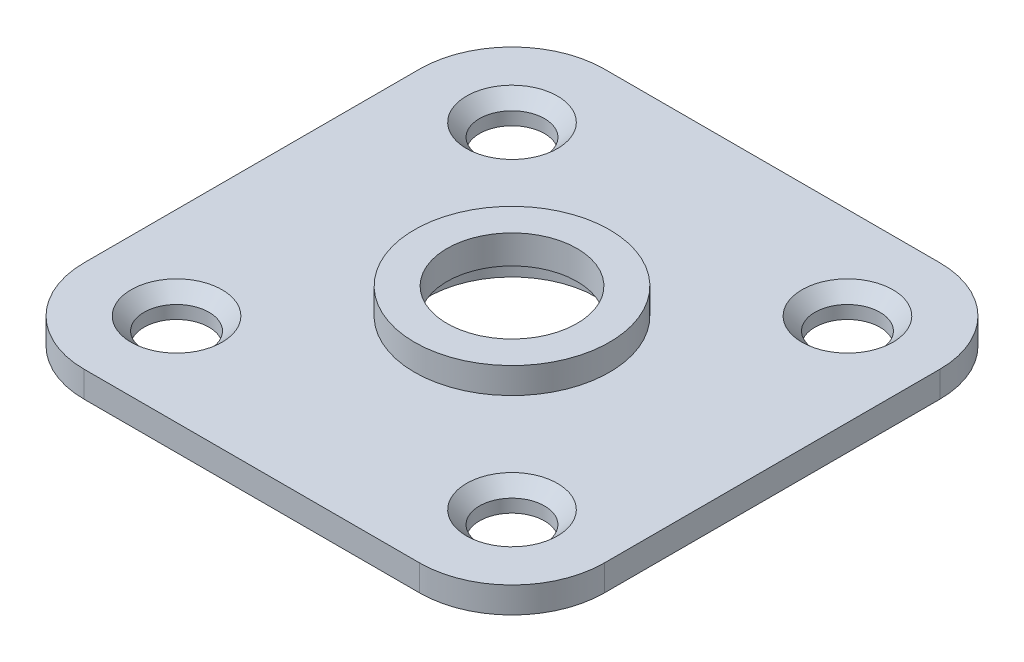
SolidWorks part; units mm, degrees
ref_plane "Front Plane" through (0, 0, 0) normal (0, 0, 1) x (1, 0, 0)
ref_plane "Top Plane" through (0, 0, 0) normal (0, 1, 0) x (1, 0, 0)
ref_plane "Right Plane" through (0, 0, 0) normal (1, 0, 0) x (0, 0, -1)
sketch "Sketch2" plane through (0, 0, 0) normal (0, 1, 0) x (1, 0, 0)
  line L1 (-25.4, 25.4) -> (25.4, 25.4)
  line L2 (-25.4, 25.4) -> (-25.4, -25.4)
  line L3 (-25.4, -25.4) -> (25.4, -25.4)
  line L4 (25.4, 25.4) -> (25.4, -25.4)
  line L5 (-25.4, 25.4) -> (25.4, -25.4) construction
  line L6 (-25.4, -25.4) -> (25.4, 25.4) construction
  point P0 (0, 0)
  dimension "D1" = 50.8
base flange "Base-Flange1" sketch "Sketch2" thickness 2.54 reverse thickness direction no parameters "D1"=0.7366
fillet "Fillet1" radius 9.017 4 edges at (-25.4, -1.27, -25.4) (-25.4, -1.27, 25.4) (25.4, -1.27, 25.4) (25.4, -1.27, -25.4)
sketch "Sketch9" plane through (0, 0, 0) normal (0, 1, 0) x (1, 0, 0)
  circle A0 centre (0, 0) radius 9.525
  dimension "D1" = 19.05
extrude "Boss-Extrude1" add sketch "Sketch9" along normal blind 2.54
sketch "Sketch10" plane through (0, -2.54, 0) normal (0, -1, 0) x (1, 0, 0)
  circle A0 centre (0, 0) radius 8.255
  dimension "D1" = 16.51
extrude "Cut-Extrude1" cut sketch "Sketch10" against normal blind 2.286 normal cut yes
sketch "Sketch11" plane through (0, -0.254, 0) normal (0, -1, 0) x (1, 0, 0)
  circle A0 centre (0, 0) radius 6.35
  dimension "D1" = 12.7
extrude "Cut-Extrude2" cut sketch "Sketch11" against normal through all normal cut yes
sketch "Sketch12" plane through (0, -2.54, 0) normal (0, -1, 0) x (1, 0, 0)
  circle A0 centre (-16.383, -16.383) radius 3.175
  dimension "D1" = 6.35
extrude "Cut-Extrude4" cut sketch "Sketch12" against normal through all normal cut yes
mirror "Mirror1" about plane through (0, 0, 0) normal (1, 0, 0) of "Cut-Extrude4"
mirror "Mirror2" about plane through (0, 0, 0) normal (0, 0, 1) of "Mirror1", "Cut-Extrude4"
chamfer "Chamfer1" distance 1.27 angle 45 4 edges at (-16.383, 0, 19.558) (16.383, 0, 19.558) (16.383, 0, -13.208) (-16.383, 0, -13.208)
sketch "Bend-Lines1" [suppressed] plane through (0, 0, 0) normal (0, 1, 0) x (1, 0, 0)
sketch "Bounding-Box1" [suppressed] plane through (0, 0, 0) normal (0, 1, 0) x (1, 0, 0)
sheet metal parameters "Sheet-Metal1" thickness 2.54 parameters "D1"=0.7366
flat pattern "Flat-Pattern1" [suppressed]
sketch "Bend-Lines2" plane through (0, 0, 0) normal (0, 1, 0) x (1, 0, 0)
sketch3d "Bounding-Box2" [suppressed]
  line L0 (-25.4, -25.4, 0) -> (25.4, -25.4, 0) construction
  line L1 (-25.4, 25.4, 0) -> (25.4, 25.4, 0) construction
  line L2 (-25.4, -25.4, 0) -> (-25.4, 25.4, 0) construction
  line L3 (25.4, -25.4, 0) -> (25.4, 25.4, 0) construction
sheet metal parameters "Sheet-Metal2" thickness 2.54 parameters "D1"=0.7366
flat pattern "Flat-Pattern1"
sketch "Bend-Lines2" plane through (0, 0, 0) normal (0, 1, 0) x (1, 0, 0)
sketch3d "Bounding-Box2" [suppressed]
  line L0 (-25.4, -25.4, 0) -> (25.4, -25.4, 0) construction
  line L1 (-25.4, 25.4, 0) -> (25.4, 25.4, 0) construction
  line L2 (-25.4, -25.4, 0) -> (-25.4, 25.4, 0) construction
  line L3 (25.4, -25.4, 0) -> (25.4, 25.4, 0) construction
sheet metal parameters "Sheet-Metal3" thickness 2.54 parameters "D1"=0.7366
flat pattern "Flat-Pattern1"
sketch "Bend-Lines2" plane through (0, 0, 0) normal (0, 1, 0) x (1, 0, 0)
sketch3d "Bounding-Box2" [suppressed]
  line L0 (-25.4, -25.4, 0) -> (25.4, -25.4, 0) construction
  line L1 (-25.4, 25.4, 0) -> (25.4, 25.4, 0) construction
  line L2 (-25.4, -25.4, 0) -> (-25.4, 25.4, 0) construction
  line L3 (25.4, -25.4, 0) -> (25.4, 25.4, 0) construction
sheet metal parameters "Sheet-Metal4" thickness 2.54 parameters "D1"=0.7366
flat pattern "Flat-Pattern1" [suppressed]
sketch "Bend-Lines2" plane through (0, 0, 0) normal (0, 1, 0) x (1, 0, 0)
sketch3d "Bounding-Box2" [suppressed]
  line L0 (-25.4, -25.4, 0) -> (25.4, -25.4, 0) construction
  line L1 (-25.4, 25.4, 0) -> (25.4, 25.4, 0) construction
  line L2 (-25.4, -25.4, 0) -> (-25.4, 25.4, 0) construction
  line L3 (25.4, -25.4, 0) -> (25.4, 25.4, 0) construction
sketch "Sketch12-1" [suppressed] plane through (0, -2.54, 0) normal (0, -1, 0) x (1, 0, 0)
  circle A0 centre (-16.383, -16.383) radius 3.175
  dimension "D1" = 6.35
sheet metal parameters "Sheet-Metal6" thickness 2.54 parameters "D1"=0.7366
flat pattern "Flat-Pattern1" [suppressed]
sketch "Bend-Lines2" plane through (0, 0, 0) normal (0, 1, 0) x (1, 0, 0)
sketch3d "Bounding-Box2" [suppressed]
  line L0 (-25.4, -25.4, 0) -> (25.4, -25.4, 0) construction
  line L1 (-25.4, 25.4, 0) -> (25.4, 25.4, 0) construction
  line L2 (-25.4, -25.4, 0) -> (-25.4, 25.4, 0) construction
  line L3 (25.4, -25.4, 0) -> (25.4, 25.4, 0) construction
sketch "Sketch12-1" [suppressed] plane through (0, -2.54, 0) normal (0, -1, 0) x (1, 0, 0)
  circle A0 centre (-16.383, -16.383) radius 3.175
  dimension "D1" = 6.35
sheet metal parameters "Sheet-Metal7" thickness 2.54 parameters "D1"=0.7366
flat pattern "Flat-Pattern1" [suppressed]
sketch "Bend-Lines2" plane through (0, 0, 0) normal (0, 1, 0) x (1, 0, 0)
sketch3d "Bounding-Box2" [suppressed]
  line L0 (-25.4, -25.4, 0) -> (25.4, -25.4, 0) construction
  line L1 (-25.4, 25.4, 0) -> (25.4, 25.4, 0) construction
  line L2 (-25.4, -25.4, 0) -> (-25.4, 25.4, 0) construction
  line L3 (25.4, -25.4, 0) -> (25.4, 25.4, 0) construction
sketch "Sketch12-1" [suppressed] plane through (0, -2.54, 0) normal (0, -1, 0) x (1, 0, 0)
  circle A0 centre (-16.383, -16.383) radius 3.175
  dimension "D1" = 6.35
sheet metal parameters "Sheet-Metal8" thickness 2.54 parameters "D1"=0.7366
flat pattern "Flat-Pattern1" [suppressed]
sketch "Bend-Lines2" plane through (0, 0, 0) normal (0, 1, 0) x (1, 0, 0)
sketch3d "Bounding-Box2" [suppressed]
  line L0 (-25.4, -25.4, 0) -> (25.4, -25.4, 0) construction
  line L1 (-25.4, 25.4, 0) -> (25.4, 25.4, 0) construction
  line L2 (-25.4, -25.4, 0) -> (-25.4, 25.4, 0) construction
  line L3 (25.4, -25.4, 0) -> (25.4, 25.4, 0) construction
sketch "Sketch12-1" [suppressed] plane through (0, -2.54, 0) normal (0, -1, 0) x (1, 0, 0)
  circle A0 centre (-16.383, -16.383) radius 3.175
  dimension "D1" = 6.35
